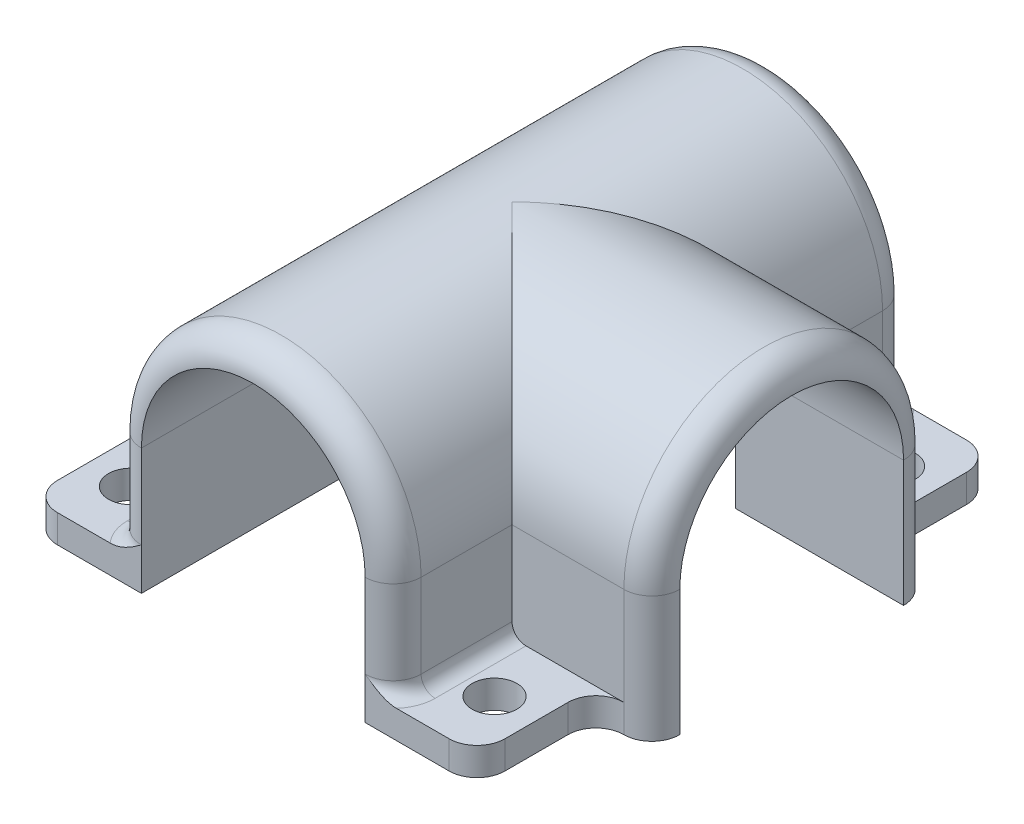
SolidWorks part; units mm, degrees
ref_plane "Front Plane" through (0, 0, 0) normal (0, 0, 1) x (1, 0, 0)
ref_plane "Top Plane" through (0, 0, 0) normal (0, 1, 0) x (1, 0, 0)
ref_plane "Right Plane" through (0, 0, 0) normal (1, 0, 0) x (0, 0, -1)
sketch "Sketch2" plane through (0, 0, 0) normal (0, 0, 1) x (1, 0, 0)
  line L0 (-8, 0) -> (-8, -9)
  line L1 (-8, -9) -> (-16, -9)
  line L2 (-16, -9) -> (-16, -7)
  line L3 (-16, -7) -> (-10, -7)
  line L4 (-10, -7) -> (-10, 0)
  line L5 (8, 0) -> (8, -9)
  line L6 (8, -9) -> (16, -9)
  line L7 (16, -9) -> (16, -7)
  line L8 (16, -7) -> (10, -7)
  line L9 (10, -7) -> (10, 0)
  arc A0 (8, 0) -> (-8, 0) centre (0, 0) ccw
  arc A1 (10, 0) -> (-10, 0) centre (0, 0) ccw
  dimension "D1" = 16
  dimension "D2" = 20
  dimension "D3" = 9
  dimension "D4" = 6
  dimension "D5" = 2
extrude "Boss-Extrude2" add sketch "Sketch2" along normal mid plane 37
sketch "Sketch3" plane through (0, 0, 0) normal (0, 1, 0) x (1, 0, 0)
  line L0 (-10, 0) -> (-16, 0) construction
  line L1 (-13, -10) -> (13, -10) construction
  line L2 (-13, -10) -> (-13, 10) construction
  line L3 (-13, 10) -> (13, 10) construction
  line L4 (13, -10) -> (13, 10) construction
  line L5 (-13, -10) -> (13, 10) construction
  line L6 (-13, 10) -> (13, -10) construction
  line L7 (-10, -18.5) -> (-10, 18.5) construction
  line L8 (-16, -18.5) -> (-16, 18.5) construction
  line L9 (0, 10) -> (0, 18.5) construction
  line L10 (-13, -14.25) -> (13, -14.25) construction
  line L11 (-13, -14.25) -> (-13, 14.25) construction
  line L12 (-13, 14.25) -> (13, 14.25) construction
  line L13 (13, -14.25) -> (13, 14.25) construction
  line L14 (-13, -14.25) -> (13, 14.25) construction
  line L15 (-13, 14.25) -> (13, -14.25) construction
  line L16 (10, 18.5) -> (-10, 18.5) construction
  point P0 (0, 0)
  point P12 (-13, 0)
  point P13 (-13, 0)
  point P14 (0, 0)
  point P23 (0, 14.25)
  dimension "D1" = 20
  dimension "D2" = 28.5
  dimension "D3" = 26
hole_wizard "M3 Clearance Hole1" positions "Sketch4" profile "Sketch5" hole size "M3" standard "ANSI Metric" end condition through all
sketch "Sketch4" plane through (0, -7, 0) normal (0, 1, 0) x (1, 0, 0)
  point P0 (-13, 14.25)
  point P3 (13, 14.25)
  point P6 (13, -14.25)
  point P9 (-13, -14.25)
sketch "Sketch5" plane through (-13, -7, -14.25) normal (1, 0, 0) x (0, 0, 1)
  line L0 (0, 0) -> (0, 2)
  line L1 (0, 2) -> (1.6, 2)
  line L2 (1.6, 2) -> (1.6, 0)
  line L5 (1.6, 0) -> (0, 0)
  line L11 (0, -6.35) -> (0, 107.95) construction
  dimension "Thru Hole Dia." = 3.2
  dimension "Thru Hole Depth" = 2
ref_plane "Plane1" through (20, 0, 0) normal (1, 0, 0) x (0, 0, -1)
sketch "Sketch6" plane through (20, 0, 0) normal (1, 0, 0) x (0, 0, -1)
  line L4 (-18.5, -9) -> (18.5, -9) construction
  line L9 (-8, 0) -> (-8, -9)
  line L11 (8, 0) -> (8, -9)
  line L13 (-10, 0) -> (-10, -9)
  line L14 (-10, -9) -> (-8, -9)
  line L15 (10, 0) -> (10, -9)
  line L16 (10, -9) -> (8, -9)
  arc A0 (8, 0) -> (-8, 0) centre (0, 0) ccw
  arc A1 (10, 0) -> (-10, 0) centre (0, 0) ccw
  dimension "D1" = 16
  dimension "D2" = 20
extrude "Boss-Extrude3" add sketch "Sketch6" against normal up to body
sketch "Sketch7" plane through (20, 0, 0) normal (1, 0, 0) x (0, 0, -1)
  line L0 (8, 0) -> (8, -7) construction
  line L1 (8, -7) -> (8, -9) construction
  line L2 (-8, -9) -> (8, -9) construction
  line L3 (-8, -9) -> (-8, -7) construction
  line L4 (-8, -7) -> (-8, 0) construction
  line L5 (8, 0) -> (8, -7)
  line L6 (8, -7) -> (8, -9)
  line L7 (-8, -9) -> (8, -9)
  line L8 (-8, -9) -> (-8, -7)
  line L9 (-8, -7) -> (-8, 0)
  arc A0 (8, 0) -> (-8, 0) centre (0, 0) ccw construction
  arc A1 (8, 0) -> (-8, 0) centre (0, 0) ccw
extrude "Cut-Extrude1" cut sketch "Sketch7" against normal up to surface (20 mm away) up to plane "Right Plane"
fillet "Fillet1" radius 2 15 edges at (16, -8, -10) (16, -8, 10) (16, -8, 18.5) (16, -8, -18.5) (-16, -8, 18.5) (-16, -8, -18.5) (20, -4.5, 10) (20, 10, 0) (20, -4.5, -10) (10, -3.5, -18.5) (-10, -3.5, -18.5) (10, -3.5, 18.5) (-10, -3.5, 18.5) (0, 10, -18.5) (0, 10, 18.5)
fillet "Fillet2" radius 1 7 edges at (9.4142, -7, -17.9142) (9.4142, -7, 17.9142) (-9.4142, -7, 17.9142) (-9.4142, -7, -17.9142) (10, -7, -13.25) (10, -7, 13.25) (-10, -7, 0)
